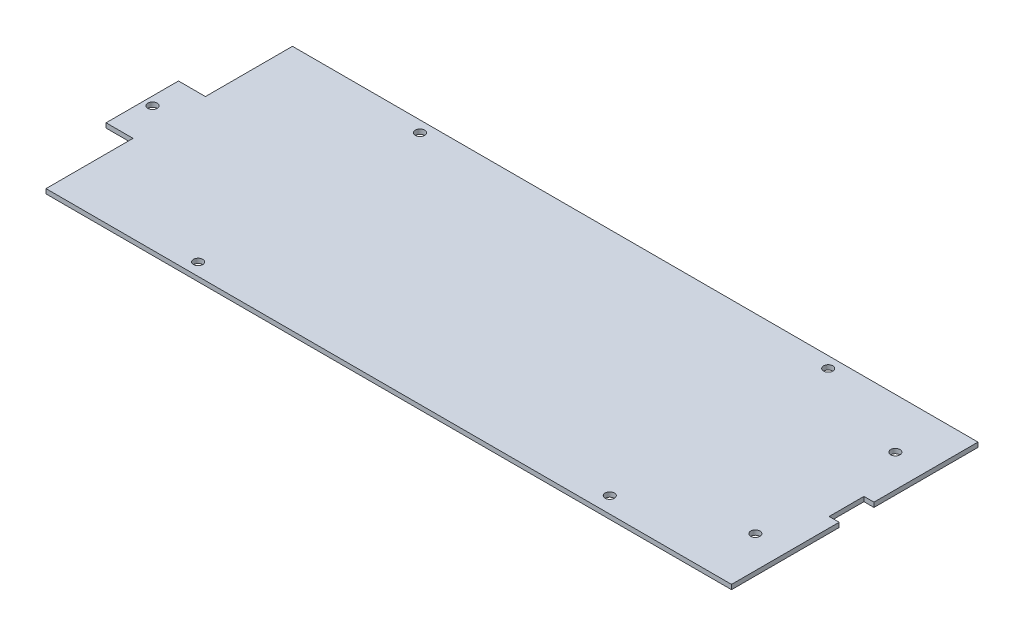
SolidWorks part; units mm, degrees
ref_plane "Front Plane" through (0, 0, 0) normal (0, 0, 1) x (1, 0, 0)
ref_plane "Top Plane" through (0, 0, 0) normal (0, 1, 0) x (1, 0, 0)
ref_plane "Right Plane" through (0, 0, 0) normal (1, 0, 0) x (0, 0, -1)
sketch "Sketch1" plane through (0, 0, 0) normal (0, 1, 0) x (1, 0, 0)
  line L0 (-302.2355, 23.5) -> (-284.7355, 23.5)
  line L1 (-284.7355, 80) -> (160.2645, 80)
  line L2 (-284.7355, 80) -> (-284.7355, 23.5)
  line L5 (-296.7465, -73.7679) -> (-296.7465, 76.0921) construction
  line L6 (-284.7355, 80) -> (-286.6881, 66.0337) construction
  line L7 (-302.2355, 23.5) -> (-302.2355, -23.5)
  line L8 (-302.2355, -23.5) -> (-284.7355, -23.5)
  line L9 (-284.7355, -23.5) -> (-284.7355, -80)
  line L10 (-284.7355, 31.0446) -> (-284.7355, 23.5) construction
  line L11 (160.2645, 80) -> (160.2645, 12.4621)
  line L12 (160.2645, 12.4621) -> (153.7645, 12.4621)
  line L13 (-302.2355, 0) -> (-26.2365, 1.1621) construction
  line L14 (161.6735, 9.4621) -> (169.6735, 9.4621) construction
  line L15 (153.7645, 12.4621) -> (153.7645, -10.1379)
  line L16 (153.7645, -10.1379) -> (160.2645, -10.1379)
  line L17 (169.6735, -7.1379) -> (161.6735, -7.1379) construction
  line L18 (160.2645, -10.1379) -> (160.2645, -80)
  line L19 (160.2645, -80) -> (-284.7355, -80)
  line L20 (-194.7355, 72.7736) -> (70.2645, 72.7736) construction
  circle A0 centre (-296.7465, 1.1621) radius 3
  circle A1 centre (-194.7355, 72.7736) radius 3
  circle A2 centre (70.2645, 72.7736) radius 3
  circle A3 centre (70.8641, -69.6343) radius 3
  circle A4 centre (-194.1265, -71.8658) radius 3
  circle A5 centre (139.1024, 47.5) radius 3
  circle A6 centre (139.4867, -43.7819) radius 3
  point P4 (0, 0)
  dimension "D9" = 6.5
  dimension "D12" = 6
  dimension "D3" = 6
  dimension "D15" = 6
  dimension "D16" = 6
  dimension "D1" = 56.5
  dimension "D2" = 56.5
  dimension "D4" = 3
  dimension "D5" = 3
  dimension "D6" = 17.5
  dimension "D7" = 445
  dimension "D8" = 69.8621
  dimension "D10" = 160
  dimension "D11" = 67.5379
  dimension "D13" = 90
  dimension "D14" = 90
  dimension "D17" = 32.5
extrude "Boss-Extrude1" add sketch "Sketch1" along normal blind 3 from offset 2 contours L8 L9 L1 L2 L0 L7 region at (-65.4054, 0, 0.0059)
